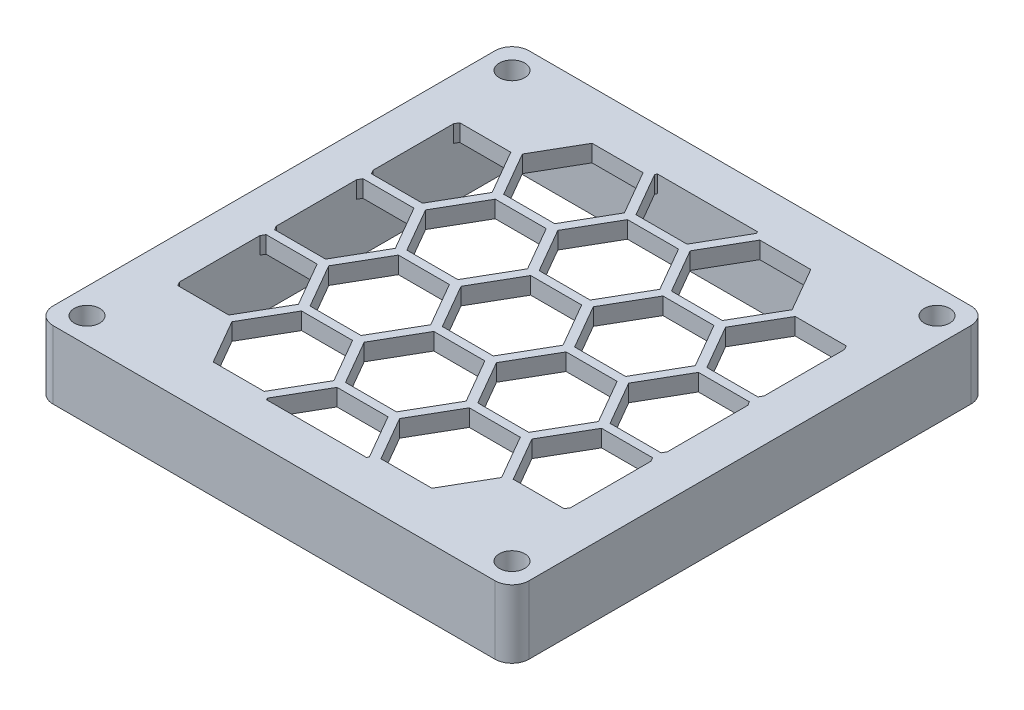
SolidWorks part; units mm, degrees
ref_plane "Front Plane" through (0, 0, 0) normal (0, 0, 1) x (1, 0, 0)
ref_plane "Top Plane" through (0, 0, 0) normal (0, 1, 0) x (1, 0, 0)
ref_plane "Right Plane" through (0, 0, 0) normal (1, 0, 0) x (0, 0, -1)
ref_axis "X" through (-88.99, 0, 0) along (1, 0, 0)
ref_axis "Y" through (0, 55, 0) along (0, -1, 0)
ref_axis "Z" through (0, 0, -88.99) along (0, 0, 1)
sketch "Sketch1" plane through (0, 0, 0) normal (0, 1, 0) x (1, 0, 0)
  line L0 (-28, 28) -> (-28, -28)
  line L1 (-25, 25) -> (25, 25) construction
  line L2 (-25, 25) -> (-25, -25) construction
  line L3 (-25, -25) -> (25, -25) construction
  line L4 (25, 25) -> (25, -25) construction
  line L5 (-25, 25) -> (25, -25) construction
  line L6 (-25, -25) -> (25, 25) construction
  line L7 (-28, -28) -> (28, -28)
  line L8 (28, 28) -> (28, -28)
  line L9 (-28, 28) -> (28, 28)
  line L10 (-23, 23) -> (-23, -23)
  line L11 (-23, -23) -> (23, -23)
  line L12 (23, 23) -> (23, -23)
  line L13 (-23, 23) -> (23, 23)
  circle A0 centre (-25, 25) radius 1.5
  circle A1 centre (25, 25) radius 1.5
  circle A2 centre (25, -25) radius 1.5
  circle A3 centre (-25, -25) radius 1.5
  point P0 (0, 0)
  dimension "D4" = 3
  dimension "D1" = 50
  dimension "D2" = 3
  dimension "D3" = 5
extrude "Boss-Extrude1" add sketch "Sketch1" along normal blind 6
extrude "Boss-Extrude2" add sketch "Sketch1<2>" along normal blind 2 from surface contours L7 L8 L9 L0 | A3 | A2 | A1 | A0 starting at face at (0, 6, 0)
sketch "Sketch1<2>" plane through (0, 0, 0) normal (0, 1, 0) x (1, 0, 0) same geometry as "Sketch1"
sketch "Sketch2" plane through (0, 6, 0) normal (0, -1, 0) x (1, 0, 0)
  line L0 (0, 0) -> (9.866, 5.6962) construction
  line L1 (3, -5.1962) -> (6, 0)
  line L2 (6, 0) -> (3, 5.1962)
  line L3 (3, 5.1962) -> (-3, 5.1962)
  line L4 (-3, 5.1962) -> (-6, 0)
  line L5 (-6, 0) -> (-3, -5.1962)
  line L6 (-3, -5.1962) -> (3, -5.1962)
  line L7 (15.866, 5.6962) -> (12.866, 10.8923)
  line L8 (12.866, 10.8923) -> (6.866, 10.8923)
  line L9 (6.866, 10.8923) -> (3.866, 5.6962)
  line L10 (3.866, 5.6962) -> (6.866, 0.5)
  line L11 (6.866, 0.5) -> (12.866, 0.5)
  line L12 (12.866, 0.5) -> (15.866, 5.6962)
  line L13 (9.866, 5.6962) -> (19.7321, 11.3923) construction
  line L14 (22.7321, 6.1962) -> (25.7321, 11.3923)
  line L15 (25.7321, 11.3923) -> (22.7321, 16.5885)
  line L16 (22.7321, 16.5885) -> (16.7321, 16.5885)
  line L17 (16.7321, 16.5885) -> (13.7321, 11.3923)
  line L18 (13.7321, 11.3923) -> (16.7321, 6.1962)
  line L19 (16.7321, 6.1962) -> (22.7321, 6.1962)
  line L20 (-3, -5.1962) -> (3, -5.1962)
  line L21 (3, 6.1962) -> (6, 11.3923)
  line L22 (6, 11.3923) -> (3, 16.5885)
  line L23 (3, 16.5885) -> (-3, 16.5885)
  line L24 (-23, -23) -> (23, -23)
  line L25 (23, -23) -> (23, 23)
  line L26 (23, 23) -> (-23, 23)
  line L27 (-23, 23) -> (-23, -23)
  line L28 (-23, -23) -> (23, -23)
  line L29 (23, -23) -> (23, 23)
  line L30 (23, 23) -> (-23, 23)
  line L31 (-23, 23) -> (-23, -23)
  line L32 (-3, 16.5885) -> (-6, 11.3923)
  line L33 (-6, 11.3923) -> (-3, 6.1962)
  line L34 (-3, 6.1962) -> (3, 6.1962)
  line L35 (12.866, 11.8923) -> (15.866, 17.0885)
  line L36 (15.866, 17.0885) -> (12.866, 22.2846)
  line L37 (12.866, 22.2846) -> (6.866, 22.2846)
  line L38 (6.866, 22.2846) -> (3.866, 17.0885)
  line L39 (3.866, 17.0885) -> (6.866, 11.8923)
  line L40 (6.866, 11.8923) -> (12.866, 11.8923)
  line L41 (3, -5.1962) -> (6, 0)
  line L42 (6, 0) -> (3, 5.1962)
  line L43 (3, 5.1962) -> (-3, 5.1962)
  line L44 (-3, 5.1962) -> (-6, 0)
  line L45 (-6, 0) -> (-3, -5.1962)
  line L46 (12.866, -10.8923) -> (15.866, -5.6962)
  line L47 (15.866, -5.6962) -> (12.866, -0.5)
  line L48 (12.866, -0.5) -> (6.866, -0.5)
  line L49 (6.866, -0.5) -> (3.866, -5.6962)
  line L50 (3.866, -5.6962) -> (6.866, -10.8923)
  line L51 (6.866, -10.8923) -> (12.866, -10.8923)
  line L52 (16.7321, -16.5885) -> (22.7321, -16.5885)
  line L53 (22.7321, -16.5885) -> (25.7321, -11.3923)
  line L54 (25.7321, -11.3923) -> (22.7321, -6.1962)
  line L55 (22.7321, -6.1962) -> (16.7321, -6.1962)
  line L56 (16.7321, -6.1962) -> (13.7321, -11.3923)
  line L57 (13.7321, -11.3923) -> (16.7321, -16.5885)
  line L58 (6.866, 0.5) -> (12.866, 0.5)
  line L59 (12.866, 0.5) -> (15.866, 5.6962)
  line L60 (15.866, 5.6962) -> (12.866, 10.8923)
  line L61 (12.866, 10.8923) -> (6.866, 10.8923)
  line L62 (6.866, 10.8923) -> (3.866, 5.6962)
  line L63 (3.866, 5.6962) -> (6.866, 0.5)
  line L64 (16.7321, -5.1962) -> (22.7321, -5.1962)
  line L65 (22.7321, -5.1962) -> (25.7321, 0)
  line L66 (25.7321, 0) -> (22.7321, 5.1962)
  line L67 (22.7321, 5.1962) -> (16.7321, 5.1962)
  line L68 (16.7321, 5.1962) -> (13.7321, 0)
  line L69 (13.7321, 0) -> (16.7321, -5.1962)
  line L70 (0, 0) -> (9.866, -5.6962) construction
  line L71 (9.866, -5.6962) -> (19.7321, -11.3923) construction
  line L72 (-6, 0) -> (-3, -5.1962)
  line L73 (-3, -5.1962) -> (3, -5.1962)
  line L74 (3, -5.1962) -> (6, 0)
  line L75 (6, 0) -> (3, 5.1962)
  line L76 (3, 5.1962) -> (-3, 5.1962)
  line L77 (-3, 5.1962) -> (-6, 0)
  line L78 (-3, -16.5885) -> (3, -16.5885)
  line L79 (3, -16.5885) -> (6, -11.3923)
  line L80 (6, -11.3923) -> (3, -6.1962)
  line L81 (3, -6.1962) -> (-3, -6.1962)
  line L82 (-3, -6.1962) -> (-6, -11.3923)
  line L83 (-6, -11.3923) -> (-3, -16.5885)
  line L84 (-6, -22.7846) -> (-3, -27.9808)
  line L85 (-3, -27.9808) -> (3, -27.9808)
  line L86 (3, -27.9808) -> (6, -22.7846)
  line L87 (6, -22.7846) -> (3, -17.5885)
  line L88 (3, -17.5885) -> (-3, -17.5885)
  line L89 (-3, -17.5885) -> (-6, -22.7846)
  line L90 (3.866, -5.6962) -> (6.866, -10.8923)
  line L91 (6.866, -10.8923) -> (12.866, -10.8923)
  line L92 (12.866, -10.8923) -> (15.866, -5.6962)
  line L93 (15.866, -5.6962) -> (12.866, -0.5)
  line L94 (12.866, -0.5) -> (6.866, -0.5)
  line L95 (6.866, -0.5) -> (3.866, -5.6962)
  line L96 (3.866, -17.0885) -> (6.866, -22.2846)
  line L97 (6.866, -22.2846) -> (12.866, -22.2846)
  line L98 (12.866, -22.2846) -> (15.866, -17.0885)
  line L99 (15.866, -17.0885) -> (12.866, -11.8923)
  line L100 (12.866, -11.8923) -> (6.866, -11.8923)
  line L101 (6.866, -11.8923) -> (3.866, -17.0885)
  line L102 (0, 0) -> (0, -11.3923) construction
  line L103 (0, -11.3923) -> (0, -22.7846) construction
  line L104 (-3, 5.1962) -> (-6, 0)
  line L105 (-6, 0) -> (-3, -5.1962)
  line L106 (-3, -5.1962) -> (3, -5.1962)
  line L107 (3, -5.1962) -> (6, 0)
  line L108 (6, 0) -> (3, 5.1962)
  line L109 (3, 5.1962) -> (-3, 5.1962)
  line L110 (-15.866, -5.6962) -> (-12.866, -10.8923)
  line L111 (-12.866, -10.8923) -> (-6.866, -10.8923)
  line L112 (-6.866, -10.8923) -> (-3.866, -5.6962)
  line L113 (-3.866, -5.6962) -> (-6.866, -0.5)
  line L114 (-6.866, -0.5) -> (-12.866, -0.5)
  line L115 (-12.866, -0.5) -> (-15.866, -5.6962)
  line L116 (-22.7321, -6.1962) -> (-25.7321, -11.3923)
  line L117 (-25.7321, -11.3923) -> (-22.7321, -16.5885)
  line L118 (-22.7321, -16.5885) -> (-16.7321, -16.5885)
  line L119 (-16.7321, -16.5885) -> (-13.7321, -11.3923)
  line L120 (-13.7321, -11.3923) -> (-16.7321, -6.1962)
  line L121 (-16.7321, -6.1962) -> (-22.7321, -6.1962)
  line L122 (-3, -6.1962) -> (-6, -11.3923)
  line L123 (-6, -11.3923) -> (-3, -16.5885)
  line L124 (-3, -16.5885) -> (3, -16.5885)
  line L125 (3, -16.5885) -> (6, -11.3923)
  line L126 (6, -11.3923) -> (3, -6.1962)
  line L127 (3, -6.1962) -> (-3, -6.1962)
  line L128 (-12.866, -11.8923) -> (-15.866, -17.0885)
  line L129 (-15.866, -17.0885) -> (-12.866, -22.2846)
  line L130 (-12.866, -22.2846) -> (-6.866, -22.2846)
  line L131 (-6.866, -22.2846) -> (-3.866, -17.0885)
  line L132 (-3.866, -17.0885) -> (-6.866, -11.8923)
  line L133 (-6.866, -11.8923) -> (-12.866, -11.8923)
  line L134 (0, 0) -> (-9.866, -5.6962) construction
  line L135 (-9.866, -5.6962) -> (-19.7321, -11.3923) construction
  line L136 (3, 5.1962) -> (-3, 5.1962)
  line L137 (-3, 5.1962) -> (-6, 0)
  line L138 (-6, 0) -> (-3, -5.1962)
  line L139 (-3, -5.1962) -> (3, -5.1962)
  line L140 (3, -5.1962) -> (6, 0)
  line L141 (6, 0) -> (3, 5.1962)
  line L142 (-12.866, 10.8923) -> (-15.866, 5.6962)
  line L143 (-15.866, 5.6962) -> (-12.866, 0.5)
  line L144 (-12.866, 0.5) -> (-6.866, 0.5)
  line L145 (-6.866, 0.5) -> (-3.866, 5.6962)
  line L146 (-3.866, 5.6962) -> (-6.866, 10.8923)
  line L147 (-6.866, 10.8923) -> (-12.866, 10.8923)
  line L148 (-16.7321, 16.5885) -> (-22.7321, 16.5885)
  line L149 (-22.7321, 16.5885) -> (-25.7321, 11.3923)
  line L150 (-25.7321, 11.3923) -> (-22.7321, 6.1962)
  line L151 (-22.7321, 6.1962) -> (-16.7321, 6.1962)
  line L152 (-16.7321, 6.1962) -> (-13.7321, 11.3923)
  line L153 (-13.7321, 11.3923) -> (-16.7321, 16.5885)
  line L154 (-6.866, -0.5) -> (-12.866, -0.5)
  line L155 (-12.866, -0.5) -> (-15.866, -5.6962)
  line L156 (-15.866, -5.6962) -> (-12.866, -10.8923)
  line L157 (-12.866, -10.8923) -> (-6.866, -10.8923)
  line L158 (-6.866, -10.8923) -> (-3.866, -5.6962)
  line L159 (-3.866, -5.6962) -> (-6.866, -0.5)
  line L160 (-16.7321, 5.1962) -> (-22.7321, 5.1962)
  line L161 (-22.7321, 5.1962) -> (-25.7321, 0)
  line L162 (-25.7321, 0) -> (-22.7321, -5.1962)
  line L163 (-22.7321, -5.1962) -> (-16.7321, -5.1962)
  line L164 (-16.7321, -5.1962) -> (-13.7321, 0)
  line L165 (-13.7321, 0) -> (-16.7321, 5.1962)
  line L166 (0, 0) -> (-9.866, 5.6962) construction
  line L167 (-9.866, 5.6962) -> (-19.7321, 11.3923) construction
  line L168 (6, 0) -> (3, 5.1962)
  line L169 (3, 5.1962) -> (-3, 5.1962)
  line L170 (-3, 5.1962) -> (-6, 0)
  line L171 (-6, 0) -> (-3, -5.1962)
  line L172 (-3, -5.1962) -> (3, -5.1962)
  line L173 (3, -5.1962) -> (6, 0)
  line L174 (3, 16.5885) -> (-3, 16.5885)
  line L175 (-3, 16.5885) -> (-6, 11.3923)
  line L176 (-6, 11.3923) -> (-3, 6.1962)
  line L177 (-3, 6.1962) -> (3, 6.1962)
  line L178 (3, 6.1962) -> (6, 11.3923)
  line L179 (6, 11.3923) -> (3, 16.5885)
  line L180 (6, 22.7846) -> (3, 27.9808)
  line L181 (3, 27.9808) -> (-3, 27.9808)
  line L182 (-3, 27.9808) -> (-6, 22.7846)
  line L183 (-6, 22.7846) -> (-3, 17.5885)
  line L184 (-3, 17.5885) -> (3, 17.5885)
  line L185 (3, 17.5885) -> (6, 22.7846)
  line L186 (-3.866, 5.6962) -> (-6.866, 10.8923)
  line L187 (-6.866, 10.8923) -> (-12.866, 10.8923)
  line L188 (-12.866, 10.8923) -> (-15.866, 5.6962)
  line L189 (-15.866, 5.6962) -> (-12.866, 0.5)
  line L190 (-12.866, 0.5) -> (-6.866, 0.5)
  line L191 (-6.866, 0.5) -> (-3.866, 5.6962)
  line L192 (-3.866, 17.0885) -> (-6.866, 22.2846)
  line L193 (-6.866, 22.2846) -> (-12.866, 22.2846)
  line L194 (-12.866, 22.2846) -> (-15.866, 17.0885)
  line L195 (-15.866, 17.0885) -> (-12.866, 11.8923)
  line L196 (-12.866, 11.8923) -> (-6.866, 11.8923)
  line L197 (-6.866, 11.8923) -> (-3.866, 17.0885)
  line L198 (0, 0) -> (0, 11.3923) construction
  line L199 (0, 11.3923) -> (0, 22.7846) construction
  circle A0 centre (0, 0) radius 5.1962 construction
  circle A1 centre (9.866, 5.6962) radius 5.1962 construction
  circle A2 centre (19.7321, 11.3923) radius 5.1962 construction
  circle A3 centre (0, 11.3923) radius 5.1962 construction
  circle A4 centre (9.866, 17.0885) radius 5.1962 construction
  circle A5 centre (0, 0) radius 5.1962 construction
  circle A6 centre (9.866, -5.6962) radius 5.1962 construction
  circle A7 centre (19.7321, -11.3923) radius 5.1962 construction
  circle A8 centre (9.866, 5.6962) radius 5.1962 construction
  circle A9 centre (19.7321, 0) radius 5.1962 construction
  circle A10 centre (0, 0) radius 5.1962 construction
  circle A11 centre (0, -11.3923) radius 5.1962 construction
  circle A12 centre (0, -22.7846) radius 5.1962 construction
  circle A13 centre (9.866, -5.6962) radius 5.1962 construction
  circle A14 centre (9.866, -17.0885) radius 5.1962 construction
  circle A15 centre (0, 0) radius 5.1962 construction
  circle A16 centre (-9.866, -5.6962) radius 5.1962 construction
  circle A17 centre (-19.7321, -11.3923) radius 5.1962 construction
  circle A18 centre (0, -11.3923) radius 5.1962 construction
  circle A19 centre (-9.866, -17.0885) radius 5.1962 construction
  circle A20 centre (0, 0) radius 5.1962 construction
  circle A21 centre (-9.866, 5.6962) radius 5.1962 construction
  circle A22 centre (-19.7321, 11.3923) radius 5.1962 construction
  circle A23 centre (-9.866, -5.6962) radius 5.1962 construction
  circle A24 centre (-19.7321, 0) radius 5.1962 construction
  circle A25 centre (0, 0) radius 5.1962 construction
  circle A26 centre (0, 11.3923) radius 5.1962 construction
  circle A27 centre (0, 22.7846) radius 5.1962 construction
  circle A28 centre (-9.866, 5.6962) radius 5.1962 construction
  circle A29 centre (-9.866, 17.0885) radius 5.1962 construction
  point P243 (0, 0)
  line M49 (23, -23) -> (23, 23)
  dimension "D1" = 6
  dimension "D2" = 1
  dimension "D3" = 1
  dimension "D5" = 1
  dimension "D6" = 1
  dimension "D4" = 0
  dimension "D7" = 6
extrude "Cut-Extrude1" cut sketch "Sketch2" against normal through all both and the other way through all contours L164 L165 L160 L161 L31 L162 L163 | L152 L153 L148 L149 L31 L150 L151 | L146 L147 L142 L143 L144 L145 | L196 L197 L192 L193 L194 L195 | L33 L34 L21 L22 L23 L32 | L184 L185 L180 L30 L182 L183 | L39 L40 L35 L36 L37 L38 | L18 L19 L14 L15 L16 L17 M49 | L11 L12 L7 L8 L9 L10 | L68 L69 L64 L65 L29 L66 L67 | L50 L51 L46 L47 L48 L49 | L56 L57 L52 L53 L29 L54 L55 | L5 L6 L1 L2 L3 L4 | L82 L83 L78 L79 L80 L81 | L100 L101 L96 L97 L98 L99 | L88 L89 L84 L28 L86 L87 | L114 L115 L110 L111 L112 L113 | L132 L133 L128 L129 L130 L131 | L120 L121 L116 L31 L117 L118 L119 region at (0, 6, 0) region at (9.866, 6, 5.6962) region at (19.0618, 6, 11.3923) region at (19.0618, 6, 0) region at (19.0618, 6, -11.3923) region at (0, 6, 20.6005) region at (0, 6, -20.6005) region at (-19.0618, 6, 11.3923) region at (-19.0618, 6, 0) region at (-19.0618, 6, -11.3923) region at (0, 6, 11.3923) region at (9.866, 6, 17.0885) region at (9.866, 6, -5.6962) region at (0, 6, -11.3923) region at (9.866, 6, -17.0885) region at (-9.866, 6, -5.6962) region at (-9.866, 6, -17.0885) region at (-9.866, 6, 5.6962) region at (-9.866, 6, 17.0885)
fillet "Fillet1" radius 2 4 edges at (28, 4, 28) (-28, 4, 28) (-28, 4, -28) (28, 4, -28)
